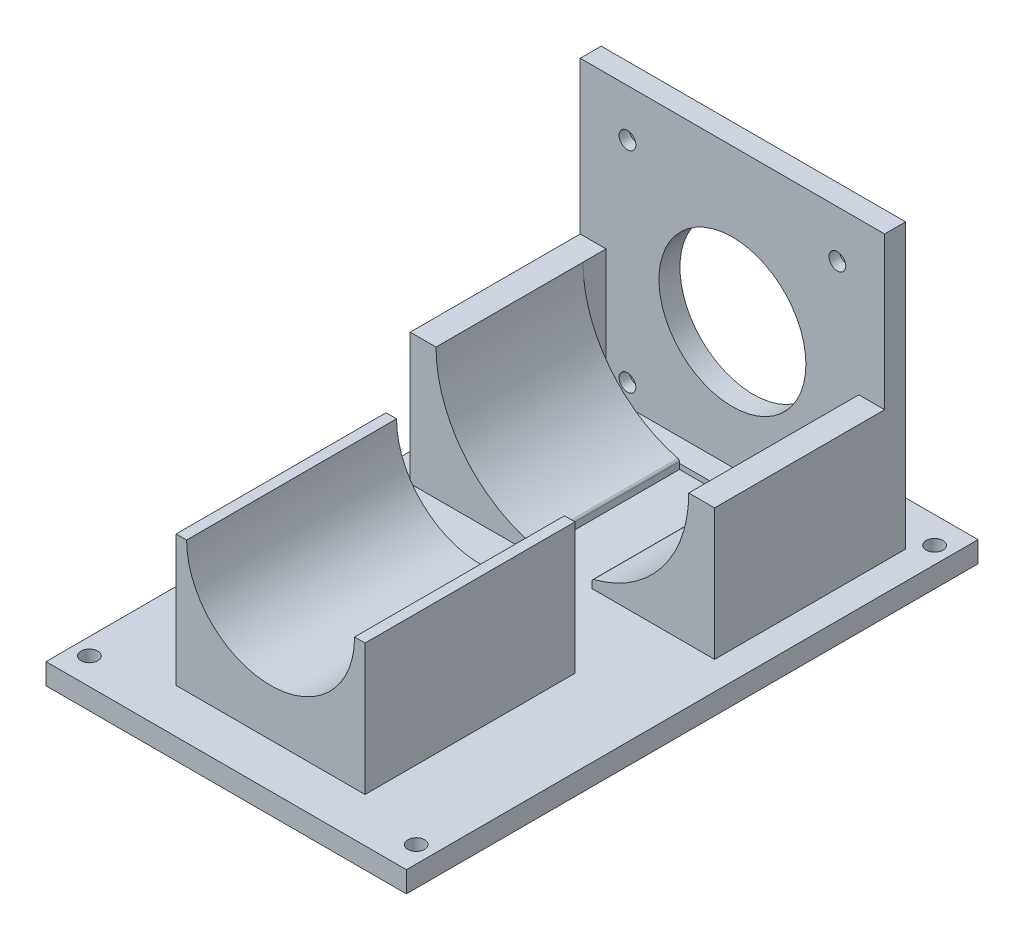
SolidWorks part; units mm, degrees
ref_plane "Front Plane" through (0, 0, 0) normal (0, 0, 1) x (1, 0, 0)
ref_plane "Top Plane" through (0, 0, 0) normal (0, 1, 0) x (1, 0, 0)
ref_plane "Right Plane" through (0, 0, 0) normal (1, 0, 0) x (0, 0, -1)
sketch "Sketch1" plane through (0, 0, 0) normal (0, 0, 1) x (1, 0, 0)
  line L0 (0, 72.5) -> (72.5, 0) construction
  line L1 (0, 0) -> (72.5, 0)
  line L2 (0, 0) -> (0, 72.5)
  line L3 (0, 72.5) -> (72.5, 72.5)
  line L4 (72.5, 0) -> (72.5, 72.5)
  line L6 (0, 0) -> (72.5, 72.5) construction
  circle A4 centre (36.25, 36.25) radius 17.5
  circle A5 centre (11.25, 61.25) radius 2
  circle A6 centre (61.25, 61.25) radius 2
  circle A7 centre (61.25, 11.25) radius 2
  circle A8 centre (11.25, 11.25) radius 2
  point P5 (11.25, 11.25)
  point P8 (61.25, 11.25)
  point P15 (36.25, 72.5)
  point P16 (0, 36.25)
  point P17 (61.25, 61.25)
  point P20 (11.25, 61.25)
  dimension "D1" = 50
  dimension "D8" = 35
  dimension "D4" = 4
  dimension "D2" = 50
  dimension "D3" = 72.5
extrude "Boss-Extrude1" add sketch "Sketch1" along normal blind 5
ref_plane "Plane1" through (0, 0, 65) normal (0, 0, 1) x (1, 0, 0)
sketch "Sketch18" plane through (0, 0, 0) normal (0, 0, 1) x (1, 0, 0)
  circle A0 centre (61.25, 61.25) radius 5
  circle A1 centre (11.25, 61.25) radius 5
  circle A2 centre (61.25, 11.25) radius 5
  circle A3 centre (11.25, 11.25) radius 5
  dimension "D1" = 10
sketch "Sketch5" plane through (0, 0, 65) normal (0, 0, 1) x (1, 0, 0)
  line L0 (0, 0) -> (72.5, 0)
  line L1 (13.75, 36.25) -> (16.25, 36.25)
  line L2 (13.75, 36.25) -> (13.75, 5)
  line L4 (0, 0) -> (0, 5)
  line L5 (0, 72.5) -> (0, 0) construction
  line L6 (0, 5) -> (13.75, 5)
  line L7 (36.25, 72.5) -> (36.25, 0) construction
  line L8 (72.5, 72.5) -> (0, 72.5) construction
  line L9 (72.5, 5) -> (58.75, 5)
  line L11 (72.5, 0) -> (72.5, 5)
  line L12 (58.75, 36.25) -> (56.25, 36.25)
  line L13 (58.75, 36.25) -> (58.75, 5)
  arc A2 (16.25, 36.25) -> (56.25, 36.25) centre (36.25, 36.25) ccw
  dimension "D4" = 20
  dimension "D2" = 5
  dimension "D3" = 22.5
extrude "Boss-Extrude2" add sketch "Sketch5" along normal blind 50 separate body
extrude "Cut-Extrude1" cut sketch "Sketch18" along direction (0, 0, -1) on the side of the normal blind 2.5
ref_plane "Plane4" through (0, 5, 0) normal (0, 1, 0) x (1, 0, 0)
sketch "Sketch7" plane through (0, 0, 5) normal (0, 0, 1) x (1, 0, 0)
  line L0 (0, 0) -> (72.5, 0)
  line L5 (72.5, 0) -> (72.5, 36.25)
  line L6 (72.5, 0) -> (72.5, 72.5) construction
  line L7 (72.5, 36.25) -> (66.35, 36.25)
  line L8 (66.35, 36.25) -> (66.35, 5)
  line L9 (72.5, 5) -> (58.75, 5) construction
  line L10 (66.35, 5) -> (6.15, 5)
  line L12 (6.15, 5) -> (6.15, 36.25)
  line L13 (6.15, 36.25) -> (0, 36.25)
  line L14 (0, 72.5) -> (0, 0) construction
  line L15 (0, 36.25) -> (0, 0)
  point P4 (0, 0)
  dimension "D1" = 60.2
extrude "Boss-Extrude3" add sketch "Sketch7" along normal blind 5.5
sketch "Sketch8" plane through (0, 0, 65) normal (0, 0, 1) x (1, 0, 0)
  line L1 (0, 0) -> (72.5, 0)
  line L2 (0, 0) -> (0, 5)
  line L3 (0, 5) -> (72.5, 5)
  line L4 (72.5, 0) -> (72.5, 5)
extrude "Boss-Extrude4" add sketch "Sketch8" against normal up to surface (54.5 mm away) up to face at (36.25, 19.375, 10.5)
ref_plane "Plane3" through (0, 0, 10.5) normal (0, 0, 1) x (1, 0, 0)
sketch "Sketch11" plane through (0, 0, 10.5) normal (0, 0, 1) x (1, 0, 0)
  line L0 (0, 5) -> (29.1474, 5)
  line L1 (66.35, 5) -> (6.15, 5) construction
  line L2 (72.5, 5) -> (43.3526, 5)
  line L3 (0, 72.5) -> (72.5, 0) construction
  line L4 (29.1474, 7) -> (29.1474, 5)
  line L5 (43.3526, 5) -> (43.3526, 7)
  line L12 (6.15, 36.25) -> (0, 36.25)
  line L13 (0, 36.25) -> (0, 5)
  line L14 (66.35, 36.25) -> (72.5, 36.25)
  line L15 (72.5, 36.25) -> (72.5, 5)
  arc A0 (6.15, 36.25) -> (29.1474, 7) centre (36.25, 36.25) ccw
  arc A1 (66.35, 36.25) -> (43.3526, 7) centre (36.25, 36.25) cw
  dimension "D1" = 2
extrude "Boss-Extrude5" add sketch "Sketch11" along normal blind 35
sketch "Sketch17" plane through (0, 5, 0) normal (0, 1, 0) x (1, 0, 0)
  line L0 (6.15, -5) -> (6.15, -10.5)
  line L1 (-37.8926, -10.5) -> (37.8926, -10.5) construction
  line L2 (6.15, -45.5) -> (6.15, -10.5) construction
  line L3 (6.15, -10.5) -> (66.4659, -10.5)
  line L4 (66.4659, -10.5) -> (66.35, -5)
  line L5 (66.35, -5) -> (6.15, -5)
extrude "Boss-Extrude7" add sketch "Sketch17" along normal blind 1.25
sketch "Sketch12" plane through (0, 0, 0) normal (0, 1, 0) x (1, 0, 0)
  line L0 (-6.6663, -125.5741) -> (79.1663, 10.5741) construction
  line L1 (-6.6663, 10.5741) -> (79.1663, -125.5741) construction
  line L2 (-6.6663, -125.5741) -> (79.1663, -125.5741)
  line L3 (-6.6663, -125.5741) -> (-6.6663, 10.5741)
  line L4 (-6.6663, 10.5741) -> (79.1663, 10.5741)
  line L5 (79.1663, -125.5741) -> (79.1663, 10.5741)
  line L6 (-3.3331, 10.5741) -> (-3.3331, -125.5741) construction
  line L8 (14.3178, 10.5741) -> (14.3178, 0) construction
  line L9 (72.5, 0) -> (0, 0) construction
  line L11 (75.8331, 10.5741) -> (75.8331, -125.5741) construction
  line L12 (72.5, -57.5) -> (79.1663, -57.5) construction
  line L14 (72.5, -45.5) -> (72.5, -5) construction
  line L15 (-6.6663, -3.6553) -> (0, -3.6553) construction
  line L16 (0, -5) -> (0, 0) construction
  circle A0 centre (-2.6665, 4.2296) radius 2
  circle A1 centre (75.1665, 4.2296) radius 2
  circle A2 centre (75.1665, -119.2296) radius 2
  circle A3 centre (-2.6665, -119.2296) radius 2
  point P2 (0, 0)
  point P3 (72.9389, 4.0451)
  point P21 (75.8331, -57.5)
  point P26 (-3.3331, -3.6553)
  point P34 (-2.9389, 4.0451)
  point P37 (-2.9389, -100.3951)
  point P38 (72.9389, -100.3951)
  dimension "D6" = 4
  dimension "D1" = 12.5
  dimension "D2" = 12.5
  dimension "D7" = 5
  dimension "D8" = 5
  dimension "D9" = 5
  dimension "D10" = 5
extrude "Boss-Extrude6" add sketch "Sketch12" along normal up to surface (5 mm away) up to face at (36.25, 5, 66.0833)
fillet "Fillet10" radius 0.5 2 edges at (43.3526, 7, 28) (29.1474, 7, 28)
ref_plane "Plane8" through (0, 0, 45.5) normal (0, 0, 1) x (1, 0, 0)
